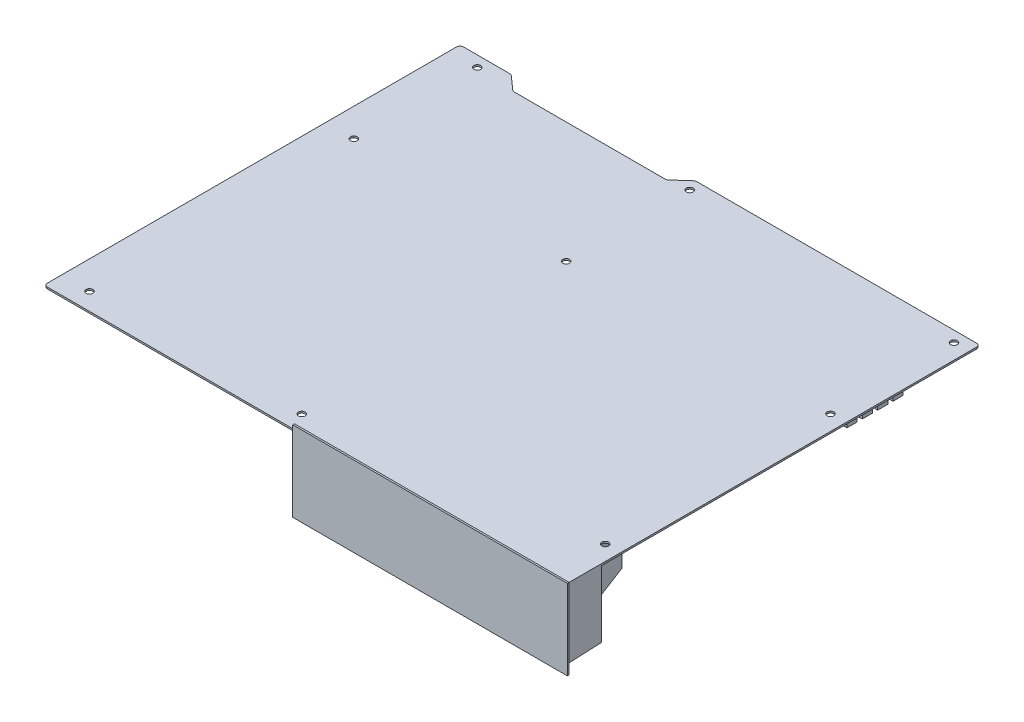
SolidWorks part; units mm, degrees
ref_plane "Front" through (0, 0, 0) normal (0, 0, 1) x (1, 0, 0)
ref_plane "Top" through (0, 0, 0) normal (0, 1, 0) x (1, 0, 0)
ref_plane "Right" through (0, 0, 0) normal (1, 0, 0) x (0, 0, -1)
sketch "Sketch1" plane through (0, 0, 0) normal (0, 1, 0) x (1, 0, 0)
  line L0 (-122.4, 121.92) -> (-122.4, 113.92) construction
  line L2 (-152.4, 121.92) -> (-152.4, -121.92)
  line L3 (-152.4, -121.92) -> (152.4, -121.92)
  line L4 (152.4, 121.92) -> (152.4, -121.92)
  line L7 (-122.4, 113.92) -> (-14.4, 113.92) construction
  line L8 (-14.4, 113.92) -> (-14.4, 121.92) construction
  line L9 (-152.4, 121.92) -> (-122.4, 121.92)
  line L10 (-14.4, 121.92) -> (152.4, 121.92)
  line L11 (-113.4, 113.92) -> (-23.4, 113.92)
  line L12 (-113.4, 113.92) -> (-122.4, 121.92)
  line L13 (-23.4, 113.92) -> (-14.4, 121.92)
  line L14 (-152.4, -111.76) -> (152.4, -111.76) construction
  line L15 (-152.4, 43.18) -> (152.4, 43.18) construction
  line L16 (-152.4, 115.57) -> (152.4, 115.57) construction
  line L17 (-135.89, -121.92) -> (-135.89, 121.92) construction
  line L18 (-11.43, -121.92) -> (-11.43, 115.57) construction
  line L19 (143.51, -121.92) -> (143.51, 121.92) construction
  circle A0 centre (-11.43, -111.76) radius 1.9812
  circle A1 centre (143.51, -88.9) radius 1.9812
  circle A2 centre (-135.89, 43.18) radius 1.9812
  circle A3 centre (-11.43, 115.57) radius 1.9812
  circle A4 centre (-135.89, 115.57) radius 1.9812
  circle A5 centre (143.51, 115.57) radius 1.9812
  circle A6 centre (-135.89, -111.76) radius 1.9812
  circle A7 centre (143.51, 43.18) radius 1.9812
  circle A8 centre (-11.43, 43.18) radius 1.9812
  point P0 (0, 0)
  point P12 (-68.4, 113.92)
  point P13 (-68.4, 113.92)
  dimension "D13" = 3.9624
  dimension "D1" = 304.8
  dimension "D2" = 243.84
  dimension "D3" = 30
  dimension "D4" = 108
  dimension "D5" = 90
  dimension "D6" = 8
  dimension "D7" = 227.33
  dimension "D8" = 10.16
  dimension "D9" = 154.94
  dimension "D10" = 124.46
  dimension "D11" = 279.4
  dimension "D12" = 16.51
  dimension "D14" = 22.86
extrude "Boss-Extrude1" add sketch "Sketch1" along normal blind 1
fillet "Fillet1" radius 2 4 edges at (-14.4, 0.5, -121.92) (-23.4, 0.5, -113.92) (-122.4, 0.5, -121.92) (-113.4, 0.5, -113.92)
fillet "Fillet2" radius 2 3 edges at (-152.4, 0.5, 121.92) (152.4, 0.5, -121.92) (-152.4, 0.5, -121.92)
sketch "Sketch2" plane through (0, 0, 0) normal (0, -1, 0) x (1, 0, 0)
  line L0 (152.4, 121.92) -> (152.4, -119.92) construction
  line L1 (-2.6, 121.92) -> (152.4, 121.92)
  line L2 (-2.6, 121.92) -> (-2.6, 99.92)
  line L4 (152.4, 121.92) -> (152.4, 99.92)
  line L5 (152.4, 99.92) -> (134.32, 91.3694)
  line L6 (134.32, 91.3694) -> (122.5293, 57.92)
  line L7 (-150.4, 121.92) -> (152.4, 121.92) construction
  line L8 (24.5293, 57.92) -> (122.5293, 57.92)
  line L9 (-2.6, 99.92) -> (24.5293, 57.92)
  dimension "D1" = 155
  dimension "D2" = 22
  dimension "D3" = 98
  dimension "D4" = 50
  dimension "D5" = 20
  dimension "D6" = 64
extrude "Boss-Extrude2" add sketch "Sketch2" along normal blind 40
sketch "Sketch3" plane through (0, 0, 121.92) normal (0, 0, 1) x (1, 0, 0)
  line L0 (152.4, -40) -> (-2.6, -40) construction
  line L1 (155.4, -43) -> (-5.6, -43)
  line L2 (155.4, -43) -> (155.4, 4)
  line L3 (155.4, 4) -> (-5.6, 4)
  line L4 (-5.6, -43) -> (-5.6, 4)
  line L5 (-150.4, 1) -> (152.4, 1) construction
  line L6 (152.4, 1) -> (152.4, -40) construction
  line L7 (-2.6, -40) -> (-2.6, 0) construction
  dimension "D1" = 3
  dimension "D2" = 3
  dimension "D3" = 3
  dimension "D4" = 3
extrude "Boss-Extrude3" add sketch "Sketch3" along normal blind 1
sketch "Sketch4" plane through (0, 0, 0) normal (1, 0, 0) x (0, 0, -1)
  line L2 (-55.6754, -37) -> (-121.92, -40)
  line L5 (-55.6754, -37) -> (-55.6754, -43.769)
  line L6 (-55.6754, -43.769) -> (-121.92, -43.769)
  line L7 (-121.92, -43.769) -> (-121.92, -40)
extrude "Cut-Extrude1" cut sketch "Sketch4" along normal mid plane 450
sketch "Sketch5" plane through (0, 0, 0) normal (0, -1, 0) x (1, 0, 0)
  line L0 (150.4, -121.92) -> (-13.6396, -121.92) construction
  line L1 (-2.6, -85.92) -> (137.4, -85.92)
  line L2 (-2.6, -85.92) -> (-2.6, -91.92)
  line L3 (-2.6, -91.92) -> (137.4, -91.92)
  line L4 (137.4, -85.92) -> (137.4, -91.92)
  line L5 (152.4, 99.92) -> (152.4, -119.92) construction
  dimension "D1" = 140
  dimension "D2" = 30
  dimension "D3" = 15
  dimension "D4" = 6
extrude "Boss-Extrude4" add sketch "Sketch5" along normal blind 5
sketch "Sketch6" plane through (0, -5, 0) normal (0, -1, 0) x (1, 0, 0)
  line L0 (-2.6, -91.92) -> (137.4, -91.92) construction
  line L1 (137.4, -85.92) -> (131.4, -85.92)
  line L2 (137.4, -85.92) -> (137.4, -91.92)
  line L3 (137.4, -91.92) -> (131.4, -91.92)
  line L4 (131.4, -85.92) -> (131.4, -91.92)
  line L6 (-2.6, -85.92) -> (3.4, -85.92)
  line L7 (-2.6, -85.92) -> (-2.6, -91.92)
  line L8 (-2.6, -91.92) -> (3.4, -91.92)
  line L9 (3.4, -85.92) -> (3.4, -91.92)
  dimension "D1" = 6
  dimension "D2" = 6
extrude "Boss-Extrude5" add sketch "Sketch6" along normal blind 12
sketch "Sketch7" plane through (0, -17, 0) normal (0, -1, 0) x (1, 0, 0)
  line L1 (-0.1, -88.17) -> (134.9, -88.17)
  line L2 (-0.1, -88.17) -> (-0.1, -89.67)
  line L3 (-0.1, -89.67) -> (134.9, -89.67)
  line L4 (134.9, -88.17) -> (134.9, -89.67)
  line L6 (137.4, -85.92) -> (-2.6, -85.92) construction
  line L8 (137.4, -91.92) -> (137.4, -85.92) construction
  dimension "D1" = 1.5
  dimension "D2" = 2.25
  dimension "D3" = 135
  dimension "D4" = 2.5
extrude "Cut-Extrude2" cut sketch "Sketch7" against normal blind 15
pattern_linear "LPattern2" count 4 spacing 9 along (0, 0, 1) of "Boss-Extrude5", "Cut-Extrude2", "Boss-Extrude4"
sketch "Sketch8" plane through (0, 0, 0) normal (0, -1, 0) x (1, 0, 0)
  line L0 (-152.4, -119.92) -> (-152.4, 119.92) construction
  line L1 (-35.4, 78.92) -> (-29.4, 78.92)
  line L2 (-35.4, 78.92) -> (-35.4, -10.08)
  line L3 (-35.4, -10.08) -> (-29.4, -10.08)
  line L4 (-29.4, 78.92) -> (-29.4, -10.08)
  line L5 (-150.4, 121.92) -> (-5.6, 121.92) construction
  line L6 (-33.4, 76.92) -> (-31.4, 76.92)
  line L7 (-33.4, 76.92) -> (-33.4, -8.08)
  line L8 (-33.4, -8.08) -> (-31.4, -8.08)
  line L9 (-31.4, 76.92) -> (-31.4, -8.08)
  dimension "D1" = 117
  dimension "D2" = 6
  dimension "D3" = 89
  dimension "D4" = 2
  dimension "D5" = 2
  dimension "D6" = 85
  dimension "D7" = 2
  dimension "D8" = 43
extrude "Boss-Extrude6" add sketch "Sketch8" along normal blind 12
sketch "Sketch9" plane through (0, 0, 0) normal (0, -1, 0) x (1, 0, 0)
  line L0 (150.4, -121.92) -> (-13.6396, -121.92) construction
  line L1 (37.4, 13.08) -> (72.4, 13.08)
  line L2 (37.4, 13.08) -> (37.4, -16.92)
  line L3 (37.4, -16.92) -> (72.4, -16.92)
  line L4 (72.4, 13.08) -> (72.4, -16.92)
  line L5 (152.4, 99.92) -> (152.4, -119.92) construction
  dimension "D1" = 105
  dimension "D2" = 30
  dimension "D3" = 35
  dimension "D4" = 80
extrude "Boss-Extrude7" add sketch "Sketch9" along normal blind 4
